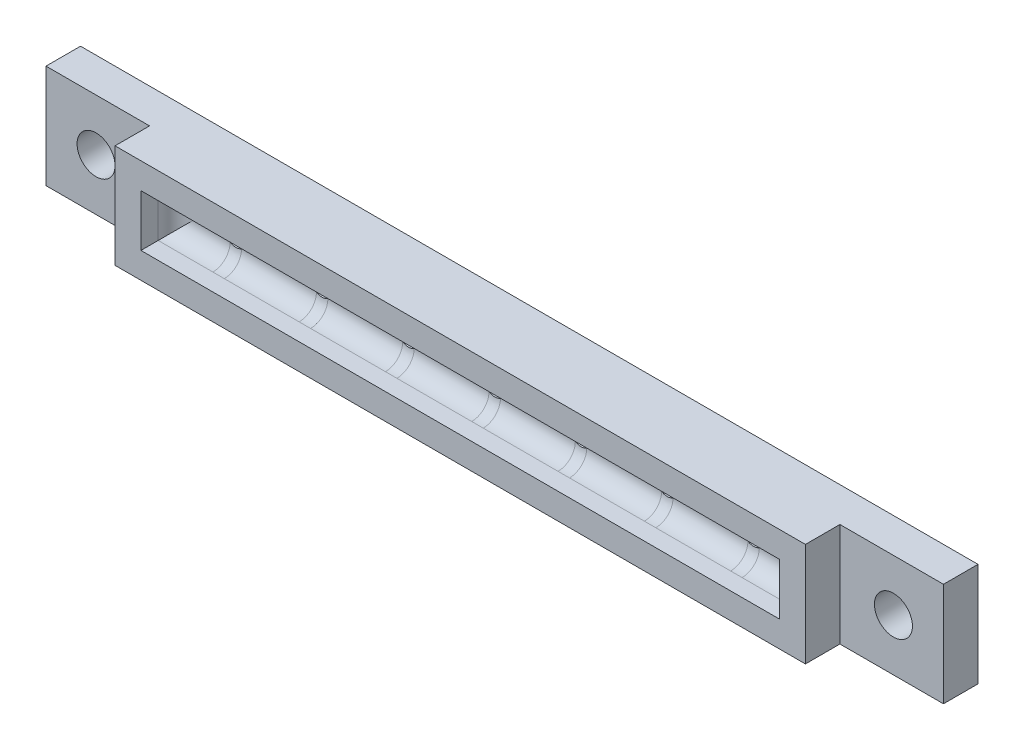
SolidWorks part; units mm, degrees
ref_plane "Front Plane" through (0, 0, 0) normal (0, 0, 1) x (1, 0, 0)
ref_plane "Top Plane" through (0, 0, 0) normal (0, 1, 0) x (1, 0, 0)
ref_plane "Right Plane" through (0, 0, 0) normal (1, 0, 0) x (0, 0, -1)
sketch "Sketch1" plane through (0, 0, 0) normal (0, 0, 1) x (1, 0, 0)
  line L1 (-23.6916, 5.285) -> (28.3084, 5.285)
  line L2 (-23.6916, 5.285) -> (-23.6916, -0.715)
  line L3 (-23.6916, -0.715) -> (28.3084, -0.715)
  line L4 (28.3084, 5.285) -> (28.3084, -0.715)
  dimension "D1" = 52
  dimension "D2" = 6
extrude "Boss-Extrude1" add sketch "Sketch1" along normal blind 4
sketch "Sketch2" plane through (0, 0, 4) normal (0, 0, 1) x (1, 0, 0)
  line L0 (-23.6916, -0.715) -> (28.3084, -0.715) construction
  line L1 (-23.6916, 5.285) -> (-17.6916, 5.285)
  line L2 (-23.6916, 5.285) -> (-23.6916, -0.715)
  line L3 (-23.6916, -0.715) -> (-17.6916, -0.715)
  line L4 (-17.6916, 5.285) -> (-17.6916, -0.715)
  line L6 (28.3084, 5.285) -> (22.3084, 5.285)
  line L7 (28.3084, 5.285) -> (28.3084, -0.715)
  line L8 (28.3084, -0.715) -> (22.3084, -0.715)
  line L9 (22.3084, 5.285) -> (22.3084, -0.715)
  dimension "D1" = 6
  dimension "D2" = 6
extrude "Cut-Extrude1" cut sketch "Sketch2" against normal blind 2
sketch "Sketch3" plane through (0, 0, 2) normal (0, 0, 1) x (1, 0, 0)
  line L0 (22.3084, -0.715) -> (28.3084, -0.715) construction
  line L1 (28.3084, -0.715) -> (28.3084, 5.285) construction
  line L2 (-23.6916, 5.285) -> (-23.6916, -0.715) construction
  line L3 (-23.6916, -0.715) -> (-17.6916, -0.715) construction
  circle A0 centre (25.4084, 2.285) radius 1.1
  circle A1 centre (-20.7916, 2.285) radius 1.1
  dimension "D1" = 2.2
  dimension "D2" = 2.2
  dimension "D3" = 3
  dimension "D4" = 2.9
  dimension "D5" = 2.9
  dimension "D6" = 3
extrude "Cut-Extrude2" cut sketch "Sketch3" against normal blind 2
sketch "Sketch4" plane through (0, 0, 4) normal (0, 0, 1) x (1, 0, 0)
  line L0 (-17.6916, -0.715) -> (22.3084, -0.715) construction
  line L1 (22.3084, 5.285) -> (22.3084, -0.715) construction
  circle A0 centre (17.3084, 2.285) radius 0.6
  circle A1 centre (12.3084, 2.285) radius 0.6
  circle A2 centre (7.3084, 2.285) radius 0.6
  circle A3 centre (2.3084, 2.285) radius 0.6
  circle A4 centre (-2.6916, 2.285) radius 0.6
  circle A5 centre (-7.6916, 2.285) radius 0.6
  circle A6 centre (-12.6916, 2.285) radius 0.6
  dimension "D1" = 1.2
  dimension "D2" = 3
  dimension "D3" = 5
  dimension "D4" = 7
extrude "Cut-Extrude3" cut sketch "Sketch4" against normal through all
sketch "Sketch5" plane through (0, 0, 4) normal (0, 0, 1) x (1, 0, 0)
  line L0 (-17.6916, -0.715) -> (22.3084, -0.715) construction
  line L1 (20.8084, 0.785) -> (-16.1916, 0.785)
  line L2 (20.8084, 0.785) -> (20.8084, 3.785)
  line L3 (20.8084, 3.785) -> (-16.1916, 3.785)
  line L4 (-16.1916, 0.785) -> (-16.1916, 3.785)
  line L5 (22.3084, 5.285) -> (22.3084, -0.715) construction
  dimension "D1" = 37
  dimension "D2" = 3
  dimension "D3" = 1.5
  dimension "D4" = 1.5
extrude "Cut-Extrude4" cut sketch "Sketch5" against normal blind 2
fillet "Fillet1" radius 1 4 edges at (20.8084, 2.285, 2) (2.3084, 3.785, 2) (-16.1916, 2.285, 2) (2.3084, 0.785, 2)
